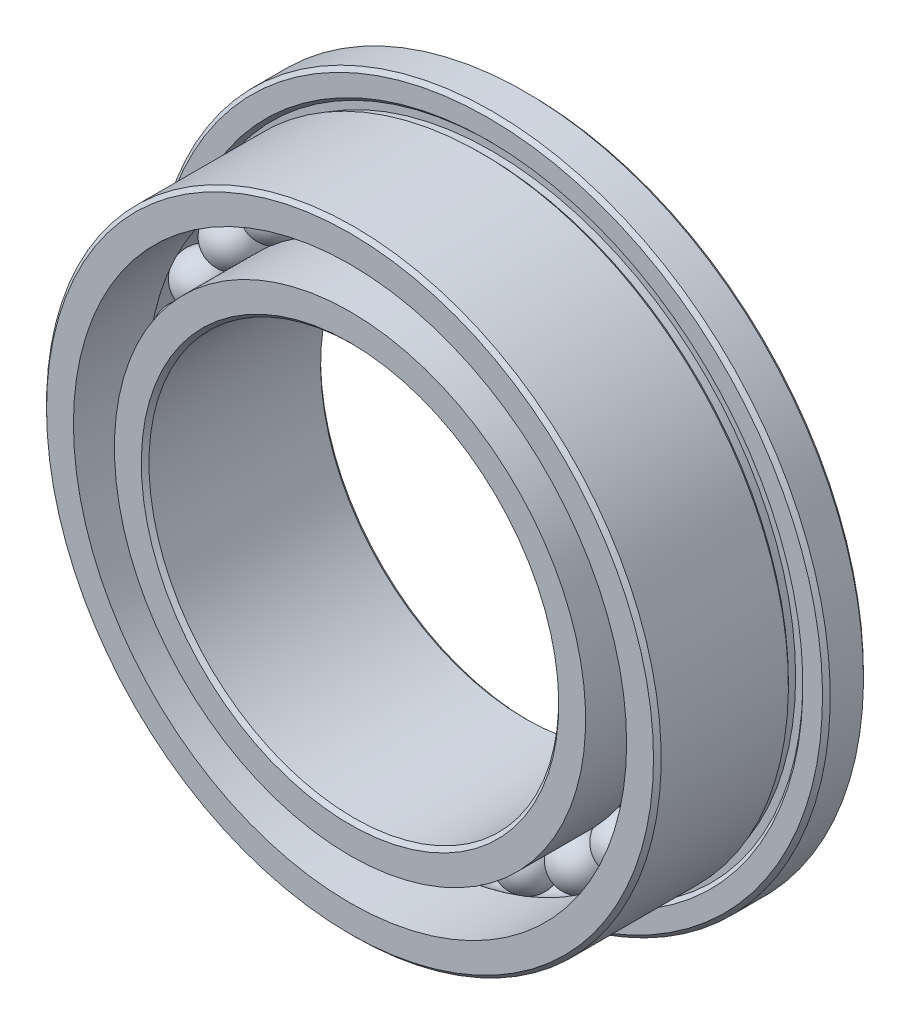
SolidWorks part; units mm, degrees
ref_plane "Front Plane" through (0, 0, 0) normal (0, 0, 1) x (1, 0, 0)
ref_plane "Top Plane" through (0, 0, 0) normal (0, 1, 0) x (1, 0, 0)
ref_plane "Right Plane" through (0, 0, 0) normal (1, 0, 0) x (0, 0, -1)
sketch "Sketch1" plane through (0, 0, 0) normal (1, 0, 0) x (0, 0, -1)
  line L0 (0, 6) -> (0, -6) construction
  line L1 (-1.75, 6) -> (1.75, 6) construction
  line L2 (0, 0) -> (1.75, 0) construction
  line L3 (1.75, 6.6) -> (1.75, -6.6) construction
  line L4 (1.75, -6.6) -> (0.95, -6.6) construction
  line L5 (1.75, 4) -> (0, 4) construction
  line L6 (1.75, 4) -> (1.75, -4) construction
  dimension "OD" = 12
  dimension "Width" = 3.5
  dimension "Flange Dia." = 13.2
  dimension "Flange Thickness" = 0.8
  dimension "ID" = 8
sketch "Sketch2" plane through (0, 0, 0) normal (1, 0, 0) x (0, 0, -1)
  line L0 (1.75, 6.6) -> (0.95, 6.6)
  line L1 (0.95, 6.6) -> (0.95, 6.1414)
  line L2 (0.8086, 6) -> (-1.75, 6)
  line L3 (-1.75, 6) -> (-1.75, 5.4)
  line L4 (-1.75, 5.4) -> (-0.3, 5.4)
  line L5 (1.75, 6.6) -> (1.75, -6.6) construction
  line L6 (1.75, 5.4) -> (1.75, 6.6)
  line L7 (1.75, 4) -> (-1.75, 4)
  line L8 (-1.75, 4) -> (-1.75, 4.6)
  line L9 (-1.75, 4.6) -> (-0.3, 4.6)
  line L10 (1.75, 4.6) -> (1.75, 4)
  line L11 (0, 6) -> (0, 4) construction
  line L12 (-0.5, 5) -> (0.5, 5) construction
  line L13 (0.3, 5.4) -> (1.75, 5.4)
  line L14 (0.3, 4.6) -> (1.75, 4.6)
  line L15 (0.95, 6.1414) -> (1.0207, 6.0707)
  line L16 (1.0207, 6.0707) -> (1.0207, 5.9293)
  line L17 (1.0207, 5.9293) -> (0.8793, 5.9293)
  line L18 (0.8793, 5.9293) -> (0.8086, 6)
  line L19 (0.95, 6) -> (1.0207, 5.9293) construction
  line L20 (1.0207, 6.0707) -> (0.8793, 5.9293) construction
  line L21 (0.8086, 6) -> (0.95, 6) construction
  line L22 (0.95, 6) -> (0.95, 6.1414) construction
  circle A0 centre (0, 5) radius 0.5 construction
  arc A1 (-0.3, 5.4) -> (0.3, 5.4) centre (0, 5) cw
  arc A2 (-0.3, 4.6) -> (0.3, 4.6) centre (0, 5) ccw
  dimension "D1" = 2
  dimension "Ball Dia." = 1
  dimension "D2" = 135
  dimension "D3" = 0.2
  dimension "D4" = 0.8
  dimension "Race Thikness" = 0.6
revolve "Revolve1" add sketch "Sketch2" angle 360 about L2
fillet "Fillet1" radius 0.075 3 edges at (0, -6.6, -1.75) (0, -6.6, -0.95) (0, -6, 1.75) profile chamfer
sketch "Sketch3" plane through (0, 0, 0) normal (0, 0, 1) x (1, 0, 0)
  line L0 (-4, 0) -> (4, 0) construction
  line L1 (-6, 0) -> (6, 0) construction
  point P5 (0, 0)
  dimension "ID2" = 8
  dimension "OD2" = 12
fillet "Fillet2" radius 0.075 2 edges at (0, -4, -1.75) (0, -4, 1.75) profile chamfer
sketch "Sketch7" plane through (0, 0, 0) normal (0, 0, 1) x (1, 0, 0)
  line L0 (0, 5.5) -> (0, 4.5)
  line L1 (0, 6.6) -> (0, -6.6) construction
  line L2 (-0.5528, 5.5) -> (0, 0) construction
  line L3 (0, 0) -> (0.5528, 5.5) construction
  line L4 (0.5528, 5.5) -> (-0.5528, 5.5) construction
  circle A0 centre (0, 5) radius 0.5 construction
  circle A1 centre (0, 0) radius 5.5 construction
  circle A2 centre (0, 0) radius 4.5 construction
  arc A4 (0, 5.5) -> (0, 4.5) centre (0, 5) ccw
  dimension "D1" = 11.478
revolve "Revolve3" add sketch "Sketch7" angle 360 about L0
pattern_circular "CirPattern3" count 27 over 360 about axis through (0, 0, 0) along (0, 0, -1) of bodies 107
sketch "Sketch8" [suppressed] plane through (0, 0, 0) normal (1, 0, 0) x (0, 0, -1)
  line L1 (-1, 2.9) -> (-0.76, 2.9)
  line L2 (-1, 2.9) -> (-1, 3.1)
  line L3 (-1, 3.1) -> (-0.76, 3.1)
  line L4 (-0.76, 2.9) -> (-0.76, 3.1)
  line L5 (1, 2.9) -> (0.76, 2.9)
  line L6 (1, 2.9) -> (1, 3.1)
  line L7 (1, 3.1) -> (0.76, 3.1)
  line L8 (0.76, 2.9) -> (0.76, 3.1)
  line L9 (1, 2.1) -> (0.76, 2.1)
  line L10 (1, 2.1) -> (1, 1.9)
  line L11 (1, 1.9) -> (0.76, 1.9)
  line L12 (0.76, 2.1) -> (0.76, 1.9)
  line L13 (-1, 2.1) -> (-0.76, 2.1)
  line L14 (-1, 2.1) -> (-1, 1.9)
  line L15 (-1, 1.9) -> (-0.76, 1.9)
  line L16 (-0.76, 2.1) -> (-0.76, 1.9)
  dimension "D1" = 0.2
  dimension "D2" = 0.24
revolve "Cut-Revolve1" [suppressed] cut sketch "Sketch8" angle 360 about L2
sketch "Sketch9" [suppressed] plane through (0, 0, 0) normal (1, 0, 0) x (0, 0, -1)
  line L0 (-0.76, 3.1) -> (-0.76, 2.7429)
  line L1 (-0.76, 2.7429) -> (-0.88, 2.535)
  line L2 (-0.88, 2.535) -> (-0.88, 1.96)
  line L3 (0.88, 1.96) -> (0.88, 1.9) construction
  line L4 (0.76, 3.1) -> (0.76, 2.7429)
  line L5 (0.76, 2.7429) -> (0.88, 2.535)
  line L6 (0.88, 2.535) -> (0.88, 1.96)
  line L7 (1, 1.9) -> (0.76, 1.9) construction
  line L8 (-0.82, 3.1) -> (-0.82, 2.7589)
  line L9 (-0.82, 2.7589) -> (-0.94, 2.5511)
  line L10 (-0.94, 2.5511) -> (-0.94, 1.96)
  line L11 (-0.76, 3.1) -> (-0.82, 3.1)
  line L12 (-0.88, 1.96) -> (-0.94, 1.96)
  line L13 (0.82, 3.1) -> (0.82, 2.7589)
  line L14 (0.82, 2.7589) -> (0.94, 2.5511)
  line L15 (0.94, 2.5511) -> (0.94, 1.96)
  line L16 (0.76, 3.1) -> (0.82, 3.1)
  line L17 (0.88, 1.96) -> (0.94, 1.96)
  line L18 (-0.76, 2.7429) -> (-0.76, 2.6) construction
  line L19 (0.76, 2.7429) -> (0.76, 3.1) construction
  line L20 (-0.76, 1.9) -> (-1, 1.9) construction
  line L22 (-0.88, 1.96) -> (-0.88, 1.9) construction
  dimension "D2" = 150
  dimension "D1" = 150
  dimension "D5" = 0.24
  dimension "D3" = 0.06
  dimension "D4" = 0.06
  dimension "D6" = 0.3571
revolve "Revolve4" [suppressed] add sketch "Sketch9" angle 360 about L2
ref_axis "Center Axis 1" through (0, 0, -0.66) along (0, 0, 1)
ref_plane "Contact Plane 1" through (0, 0, -0.95) normal (0, 0, 1) x (1, 0, 0)
equation "\"Ball Dia.@Sketch2\"=\"D1@Sketch2\"*.5"
equation "\"D3@Sketch2\"=\"Flange Thickness@Sketch1\"/4"
equation "\"D1@Fillet1\"=\"Race Thikness@Sketch2\"/8"
equation "\"ID2@Sketch3\" = \"ID@Sketch1\""
equation "\"OD2@Sketch3\" = \"OD@Sketch1\""
equation "\"D1@Fillet2\"=\"Race Thikness@Sketch2\"/8"
equation "\"D1@CirPattern3\"=360/\"D1@Sketch7\"-4"
equation "\"D1@Sketch8\"=\"Race Thikness@Sketch2\"/3"
equation "\"D2@Sketch8\"=\"Race Thikness@Sketch2\"/2.5"
equation "\"D3@Sketch9\"=\"D5@Sketch9\"/4"
equation "\"D4@Sketch9\"=\"D5@Sketch9\"/4"
equation "\"D1@Sketch9\"=\"D2@Sketch9\""
equation "\"D4@Sketch2\"=\"D1@Sketch2\"*.4"
